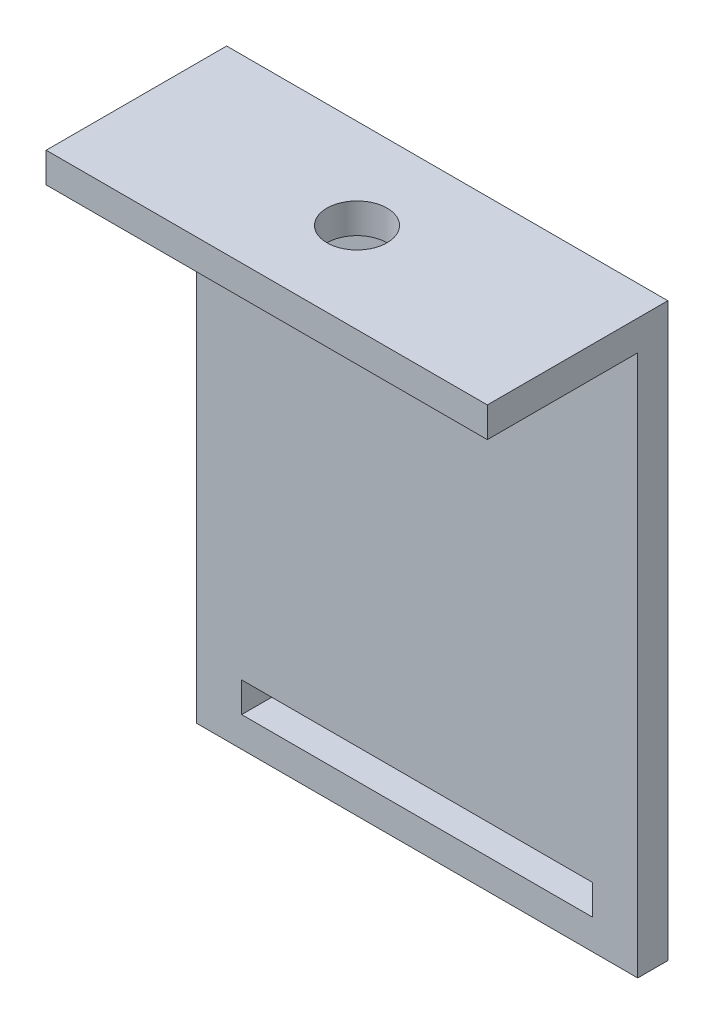
SolidWorks part; units mm, degrees
ref_plane "Piano frontale" through (0, 0, 0) normal (0, 0, 1) x (1, 0, 0)
ref_plane "Piano superiore" through (0, 0, 0) normal (0, 1, 0) x (1, 0, 0)
ref_plane "Piano destro" through (0, 0, 0) normal (1, 0, 0) x (0, 0, -1)
sketch "Schizzo8" plane through (0, 0, 0) normal (1, 0, 0) x (0, 0, -1)
  line L0 (0, 0) -> (0, 3)
  line L1 (0, 3) -> (18, 3)
  line L2 (18, 3) -> (18, -54)
  line L3 (18, -54) -> (15, -54)
  line L4 (15, -54) -> (15, 0)
  line L5 (15, 0) -> (0, 0)
  dimension "D1" = 3
  dimension "D2" = 18
  dimension "D3" = 54
  dimension "D4" = 3
extrude "Estrusione-Estrusione6" add sketch "Schizzo8" along normal blind 44
sketch "Schizzo9" plane through (0, 0, -15) normal (0, 0, 1) x (1, 0, 0)
  line L0 (44, -54) -> (0, -54) construction
  line L1 (4.5, -51) -> (39.5, -51)
  line L2 (4.5, -51) -> (4.5, -48)
  line L3 (4.5, -48) -> (39.5, -48)
  line L4 (39.5, -51) -> (39.5, -48)
  line L5 (0, 0) -> (0, -54) construction
  dimension "D1" = 3
  dimension "D2" = 35
  dimension "D3" = 3
  dimension "D4" = 4.5
extrude "Taglio-Estrusione2" cut sketch "Schizzo9" against normal blind 44
sketch "Schizzo10" plane through (0, 3, 0) normal (0, 1, 0) x (1, 0, 0)
  line L0 (0, 18) -> (44, 0) construction
  line L1 (44, 18) -> (44, 0) construction
  line L2 (44, 0) -> (44, 18) construction
  line L3 (44, 18) -> (0, 0) construction
  circle A0 centre (22, 9) radius 3
  dimension "D1" = 6
extrude "Taglio-Estrusione3" cut sketch "Schizzo10" against normal blind 10
